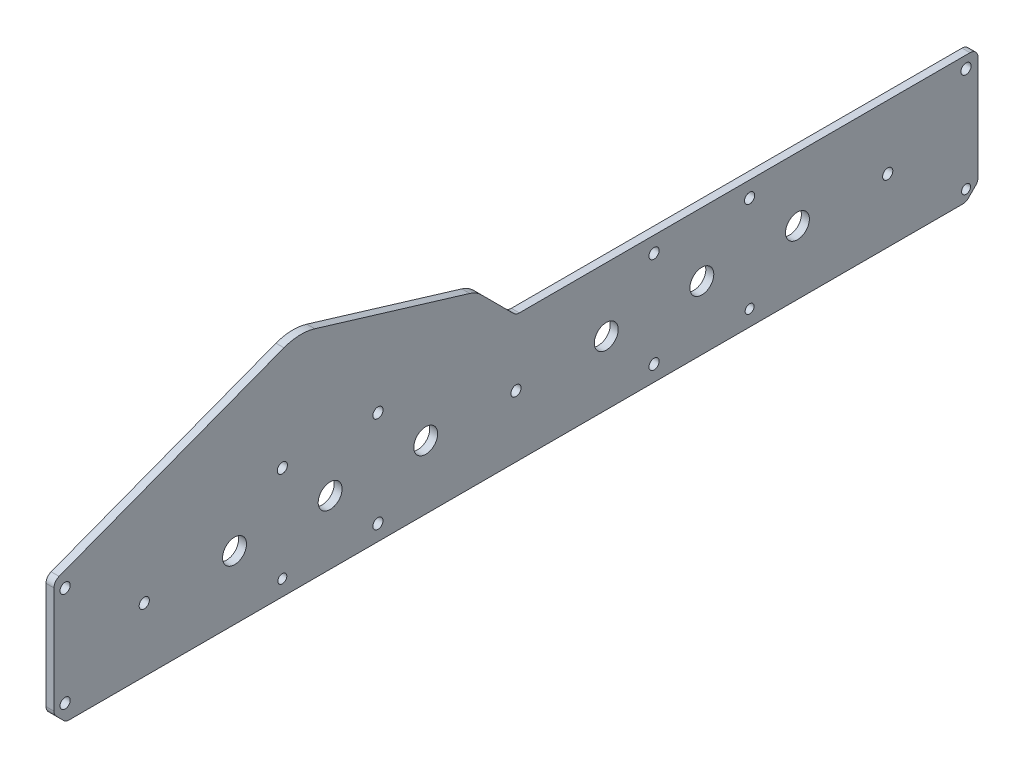
SolidWorks part; units mm, degrees
ref_plane "Front Plane" through (0, 0, 0) normal (0, 0, 1) x (1, 0, 0)
ref_plane "Top Plane" through (0, 0, 0) normal (0, 1, 0) x (1, 0, 0)
ref_plane "Right Plane" through (0, 0, 0) normal (1, 0, 0) x (0, 0, -1)
sketch "Sketch1" plane through (0, 0, 0) normal (1, 0, 0) x (0, 0, -1)
  line L0 (-184.15, 26.1937) -> (-92.4839, 61.0534)
  line L1 (-184.15, -24.6062) -> (184.15, -24.6062)
  line L2 (-184.15, -24.6062) -> (-184.15, 26.1937)
  line L3 (0, 26.1937) -> (184.15, 26.1937)
  line L4 (184.15, -24.6062) -> (184.15, 26.1937)
  line L5 (-80.1935, 61.4805) -> (-18.395, 42.7743)
  line L6 (-13.8706, 40.0644) -> (0, 26.1937)
  arc A0 (-92.4839, 61.0534) -> (-80.1935, 61.4805) centre (-85.7125, 43.2475) cw
  arc A1 (-18.395, 42.7743) -> (-13.8706, 40.0644) centre (-21.5354, 32.3996) cw
  circle A2 centre (-85.7125, 43.2475) radius 2.032 construction
  circle A3 centre (-21.5354, 32.3996) radius 1.905 construction
  point P6 (0, -24.6062)
  point P15 (0, 0)
  point P18 (-19.4882, 40.6338)
  dimension "D4" = 19.05
  dimension "D1" = 50.8
  dimension "D2" = 368.3
  dimension "D3" = 24.6062
  dimension "D5" = 45
extrude "Boss-Extrude1" add sketch "Sketch1" along normal blind 3.175
chamfer "Chamfer1" distance 4.7625 angle 45 2 edges at (1.5875, -24.6062, -184.15) (1.5875, -24.6062, 184.15)
fillet "Fillet1" radius 3.175 7 edges at (1.5875, -24.6062, -179.3875) (1.5875, -19.8437, -184.15) (1.5875, 26.1937, -184.15) (1.5875, -24.6062, 179.3875) (1.5875, -19.8437, 184.15) (1.5875, 26.1937, 0) (1.5875, 26.1937, 184.15)
sketch "Sketch4" plane through (3.175, 0, 0) normal (1, 0, 0) x (0, 0, -1)
  point P0 (-93.1246, 19.9098)
  point P1 (-55.0246, 19.9098)
  point P3 (0, 0)
  point P5 (55.0246, 19.9098)
  point P7 (93.1246, 19.9098)
  point P9 (55.0246, -18.3223)
  point P11 (-55.0246, -18.3223)
  point P13 (-179.705, 21.7487)
  point P15 (-179.705, -18.0026)
  point P17 (179.3875, 21.4312)
  point P19 (148.1579, 0.7938)
  point P21 (-148.1579, 0.7937)
hole_wizard "#8 Clearance Hole1" positions "Sketch4" profile "Sketch5" hole size "#8" standard "ANSI Inch" end condition up to next
sketch "Sketch5" plane through (3.175, 19.9098, 93.1246) normal (0, 1, 0) x (0, 0, -1)
  line L0 (0, 0) -> (0, 3.175)
  line L1 (0, 3.175) -> (2.032, 3.175)
  line L2 (2.032, 3.175) -> (2.032, 0)
  line L5 (2.032, 0) -> (0, 0)
  line L11 (0, -6.35) -> (0, 107.95) construction
  dimension "Thru Hole Dia." = 4.064
  dimension "Thru Hole Depth" = 3.175
sketch "Sketch6" plane through (3.175, 0, 0) normal (1, 0, 0) x (0, 0, -1)
  point P0 (-93.1246, -18.3223)
  point P1 (93.1246, -18.3223)
  point P3 (179.3875, -20.1161)
hole_wizard "#8 Clearance Hole2" positions "Sketch6" profile "Sketch7" hole size "#8" standard "ANSI Inch" end condition up to next
sketch "Sketch7" plane through (3.175, -18.3223, 93.1246) normal (0, 1, 0) x (0, 0, -1)
  line L0 (0, 0) -> (0, 3.175)
  line L1 (0, 3.175) -> (1.778, 3.175)
  line L2 (1.778, 3.175) -> (1.778, 0)
  line L5 (1.778, 0) -> (0, 0)
  line L11 (0, -6.35) -> (0, 107.95) construction
  dimension "Thru Hole Dia." = 3.556
  dimension "Thru Hole Depth" = 3.175
sketch "Sketch8" plane through (3.175, 0, 0) normal (1, 0, 0) x (0, 0, -1)
  point P0 (-112.1746, 0.7937)
  point P1 (-74.0746, 0.7938)
  point P3 (-35.9746, 0.7938)
  point P5 (35.9746, 0.7938)
  point P7 (74.0746, 0.7937)
  point P9 (112.1746, 0.7937)
hole_wizard "3/8 Clearance Hole1" positions "Sketch8" profile "Sketch9" hole size "3/8" standard "ANSI Inch" end condition up to next
sketch "Sketch9" plane through (3.175, 0.7937, 112.1746) normal (0, 1, 0) x (0, 0, -1)
  line L0 (0, 0) -> (0, 3.175)
  line L1 (0, 3.175) -> (4.7625, 3.175)
  line L2 (4.7625, 3.175) -> (4.7625, 0)
  line L5 (4.7625, 0) -> (0, 0)
  line L11 (0, -6.35) -> (0, 107.95) construction
  dimension "Thru Hole Dia." = 9.525
  dimension "Thru Hole Depth" = 3.175
